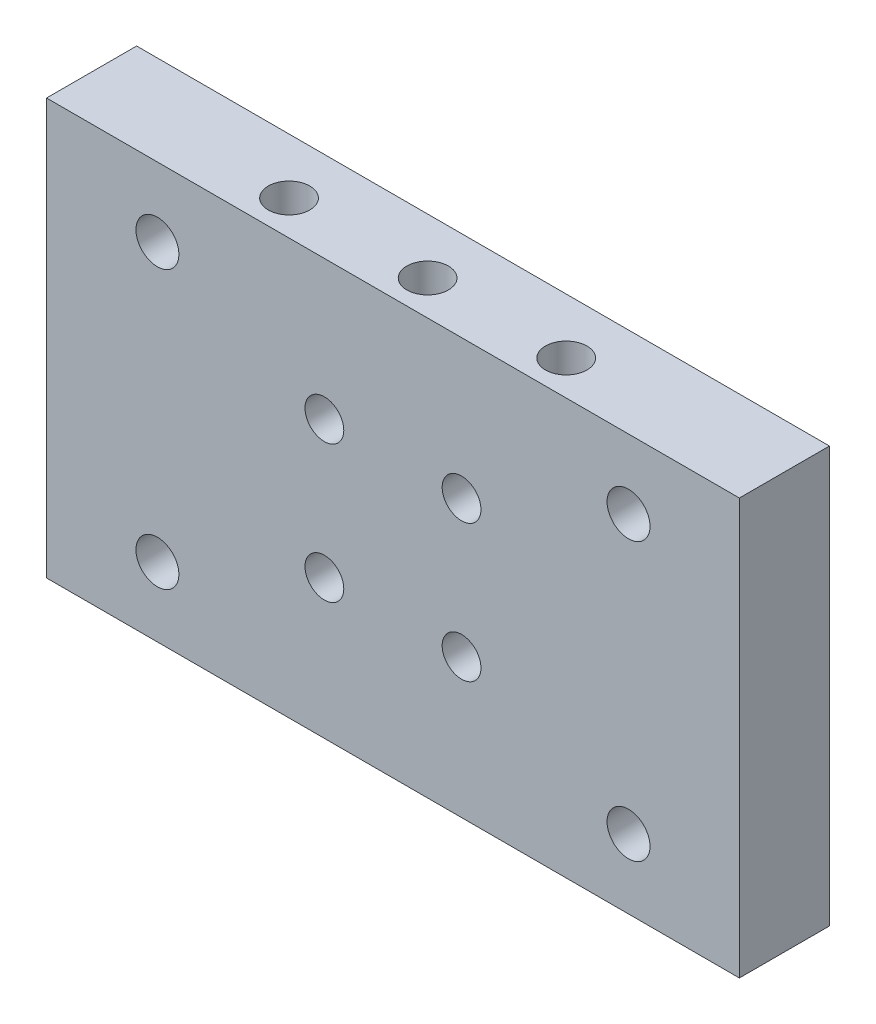
SolidWorks part; units mm, degrees
ref_plane "前视基准面" through (0, 0, 0) normal (0, 0, 1) x (1, 0, 0)
ref_plane "上视基准面" through (0, 0, 0) normal (0, 1, 0) x (1, 0, 0)
ref_plane "右视基准面" through (0, 0, 0) normal (1, 0, 0) x (0, 0, -1)
sketch "草图1" plane through (0, 0, 0) normal (0, 0, 1) x (1, 0, 0)
  line L1 (25, -15) -> (-25, -15)
  line L2 (25, -15) -> (25, 15)
  line L3 (25, 15) -> (-25, 15)
  line L4 (-25, -15) -> (-25, 15)
  line L5 (25, -15) -> (-25, 15) construction
  line L6 (25, 15) -> (-25, -15) construction
  point P0 (0, 0)
  dimension "D1" = 30
  dimension "D2" = 50
extrude "凸台-拉伸1" add sketch "草图1" along normal blind 6.5
sketch "草图2" plane through (0, 0, 6.5) normal (0, 0, 1) x (1, 0, 0)
  line L1 (4.95, -4.95) -> (-4.95, -4.95)
  line L2 (4.95, -4.95) -> (4.95, 4.95)
  line L3 (4.95, 4.95) -> (-4.95, 4.95)
  line L4 (-4.95, -4.95) -> (-4.95, 4.95)
  line L5 (4.95, -4.95) -> (-4.95, 4.95) construction
  line L6 (4.95, 4.95) -> (-4.95, -4.95) construction
  circle A0 centre (4.95, 4.95) radius 1.4
  circle A1 centre (-4.95, 4.95) radius 1.4
  circle A2 centre (-4.95, -4.95) radius 1.4
  circle A3 centre (4.95, -4.95) radius 1.4
  point P0 (0, 0)
  dimension "D1" = 9.9
  dimension "D3" = 2.8
  dimension "D2" = 9.9
extrude "切除-拉伸1" cut sketch "草图2" against normal through all contours L3 A1 L4 | L4 A1 L3 | L3 A0 L2 | L2 A0 L3 | L1 A3 L2 | L2 A3 L1 | L4 A2 L1 | L1 A2 L4 region at (-5.1481, -5.1481, 6.5) region at (-4.3558, -4.3558, 6.5) region at (4.3558, -4.3558, 6.5) region at (5.1481, -5.1481, 6.5) region at (-5.1481, 5.1481, 6.5) region at (-4.3558, 4.3558, 6.5) region at (4.3558, 4.3558, 6.5) region at (5.1481, 5.1481, 6.5)
sketch "草图4" plane through (0, 0, 0) normal (0, 0, -1) x (-1, 0, 0)
  line L0 (-25, 0) -> (-17, 0) construction
  line L1 (-25, -15) -> (-25, 15) construction
  line L2 (-17, 0) -> (-17, 10) construction
  line L3 (0, 0) -> (0, -15) construction
  line L4 (25, -15) -> (-25, -15) construction
  line L5 (17, 0) -> (17, 10) construction
  circle A0 centre (-17, 10) radius 1.55
  circle A1 centre (-17, -10) radius 1.55
  circle A2 centre (17, -10) radius 1.55
  circle A3 centre (17, 10) radius 1.55
  dimension "D1" = 3.1
  dimension "D2" = 10
  dimension "D3" = 8
extrude "切除-拉伸2" cut sketch "草图4" against normal through all
sketch "草图5" plane through (0, 15, 0) normal (0, 1, 0) x (1, 0, 0)
  circle A0 centre (-10, -4) radius 1.5
  circle A1 centre (0, -4) radius 1.5
  circle A2 centre (10, -4) radius 1.5
extrude "切除-拉伸3" cut sketch "草图5" against normal through all
